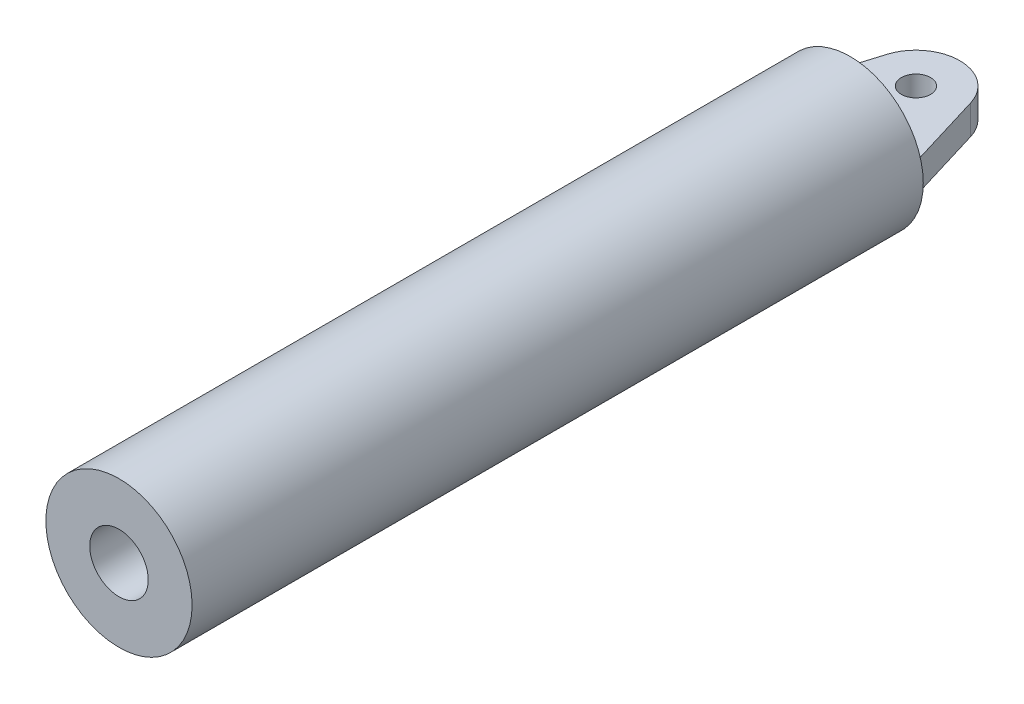
SolidWorks part; units mm, degrees
ref_plane "Front Plane" through (0, 0, 0) normal (0, 0, 1) x (1, 0, 0)
ref_plane "Top Plane" through (0, 0, 0) normal (0, 1, 0) x (1, 0, 0)
ref_plane "Right Plane" through (0, 0, 0) normal (1, 0, 0) x (0, 0, -1)
sketch "Sketch1" plane through (0, 0, 0) normal (0, 0, 1) x (1, 0, 0)
  circle A0 centre (0, 0) radius 50
  dimension "D1" = 100
extrude "Boss-Extrude1" add sketch "Sketch1" along normal blind 500
sketch "Sketch2" plane through (0, 0, 0) normal (0, 1, 0) x (1, 0, 0)
  line L0 (-45, 0) -> (-28.7083, 53.7083)
  line L1 (50, 0) -> (-50, 0) construction
  line L2 (28.7083, 53.7083) -> (45, 0)
  line L3 (-45, 0) -> (45, 0)
  circle A0 centre (0, 45) radius 10
  arc A1 (-28.7083, 53.7083) -> (28.7083, 53.7083) centre (0, 45) cw
  dimension "D1" = 20
  dimension "D2" = 30
  dimension "D3" = 45
  dimension "D4" = 45
  dimension "D5" = 45
extrude "Boss-Extrude2" add sketch "Sketch2" along normal mid plane 20
shell "Shell1" thickness 30 removed face at (50, 0, 500)
